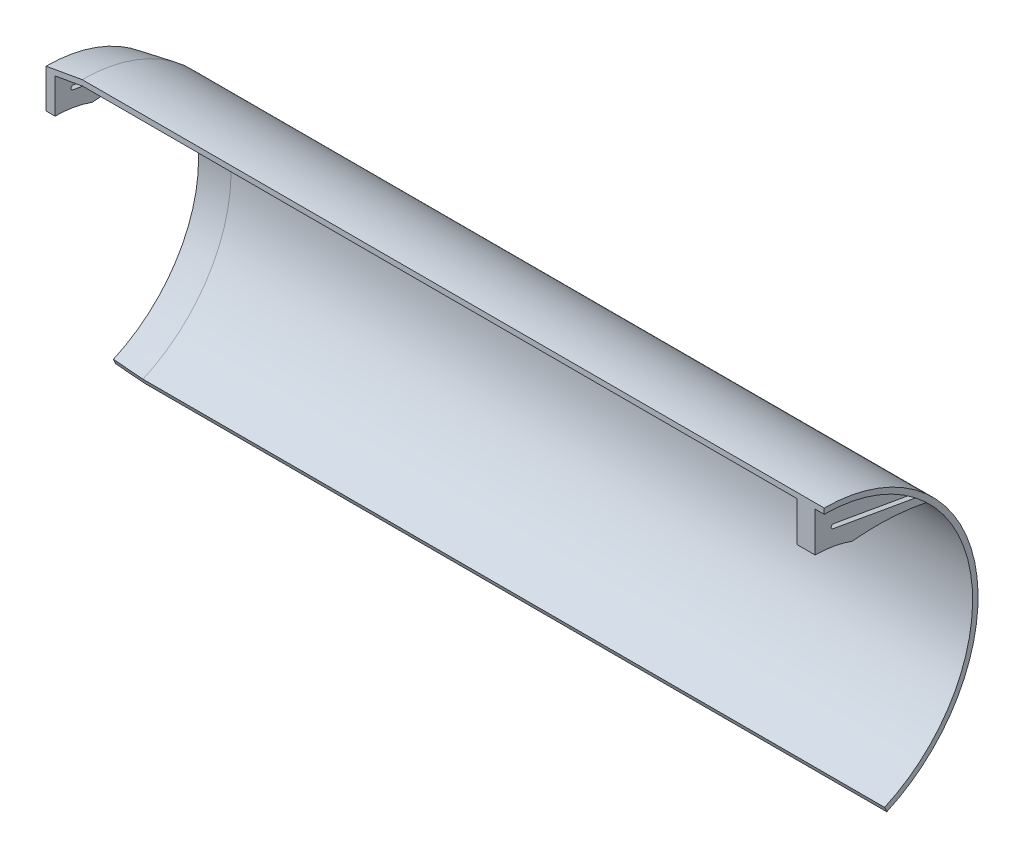
SolidWorks part; units mm, degrees
material "PETG"
ref_plane "Front Plane" through (0, 0, 0) normal (0, 0, 1) x (1, 0, 0)
ref_plane "Top Plane" through (0, 0, 0) normal (0, 1, 0) x (1, 0, 0)
ref_plane "Right Plane" through (0, 0, 0) normal (1, 0, 0) x (0, 0, -1)
curve "Curve1"
  spline degree 3 poles (0, 0, 0) (-0.0123, 3.8916, 0) (-0.0274, 8.685, 0) (0.3616, 14.0857, 0) (0.5761, 16.0905, 0) (0.7825, 17.6048, 0) (0.9862, 18.8543, 0) (1.1887, 19.9315, 0) (1.3904, 20.8857, 0) (1.5917, 21.7465, 0) (1.7927, 22.5337, 0) (1.9935, 23.2611, 0) (2.1942, 23.9386, 0) (2.3947, 24.5739, 0) (2.5952, 25.1728, 0) (2.7956, 25.7401, 0) (2.9959, 26.2796, 0) (3.1962, 26.7943, 0) (3.3965, 27.2868, 0) (3.5967, 27.7594, 0) (3.7969, 28.2139, 0) (3.9971, 28.6519, 0) (4.1973, 29.0748, 0) (4.3974, 29.4838, 0) (4.5976, 29.8799, 0) (4.7977, 30.2641, 0) (4.9978, 30.6373, 0) (5.1979, 31.0001, 0) (5.398, 31.3533, 0) (5.5981, 31.6974, 0) (5.7982, 32.033, 0) (5.9983, 32.3606, 0) (6.1984, 32.6807, 0) (6.3985, 32.9935, 0) (6.5985, 33.2996, 0) (6.7986, 33.5993, 0) (6.9986, 33.8929, 0) (7.1987, 34.1806, 0) (7.3987, 34.4628, 0) (7.5988, 34.7397, 0) (7.7988, 35.0115, 0) (7.9989, 35.2785, 0) (8.1989, 35.5408, 0) (8.399, 35.7988, 0) (8.599, 36.0524, 0) (8.799, 36.3019, 0) (8.9991, 36.5476, 0) (9.1991, 36.7894, 0) (9.3991, 37.0275, 0) (9.5992, 37.2622, 0) (9.7992, 37.4934, 0) (9.9992, 37.7214, 0) (10.1992, 37.9461, 0) (10.3993, 38.1679, 0) (10.5993, 38.3866, 0) (10.7993, 38.6025, 0) (10.9993, 38.8156, 0) (11.1993, 39.026, 0) (11.3994, 39.2338, 0) (11.5994, 39.4391, 0) (11.7994, 39.6419, 0) (11.9994, 39.8422, 0) (12.1994, 40.0403, 0) (12.3995, 40.2361, 0) (12.5995, 40.4297, 0) (12.7995, 40.6212, 0) (12.9995, 40.8106, 0) (13.1995, 40.998, 0) (13.3995, 41.1834, 0) (13.5995, 41.3668, 0) (13.7995, 41.5484, 0) (13.9996, 41.7281, 0) (14.1996, 41.9061, 0) (14.3996, 42.0823, 0) (14.5996, 42.2568, 0) (14.7996, 42.4296, 0) (14.9996, 42.6008, 0) (15.1996, 42.7705, 0) (15.3996, 42.9385, 0) (15.5996, 43.1051, 0) (15.7996, 43.2701, 0) (15.9997, 43.4337, 0) (16.1997, 43.5959, 0) (16.3997, 43.7567, 0) (16.5997, 43.9161, 0) (16.7997, 44.0742, 0) (16.9997, 44.2309, 0) (17.1997, 44.3864, 0) (17.3997, 44.5406, 0) (17.5997, 44.6936, 0) (17.7997, 44.8453, 0) (17.9997, 44.9959, 0) (18.1997, 45.1453, 0) (18.3997, 45.2936, 0) (18.5997, 45.4407, 0) (18.7997, 45.5868, 0) (18.9997, 45.7317, 0) (19.1998, 45.8756, 0) (19.3998, 46.0185, 0) (19.5998, 46.1603, 0) (19.7998, 46.3011, 0) (19.9998, 46.4409, 0) (20.1998, 46.5797, 0) (20.3998, 46.7176, 0) (20.5998, 46.8546, 0) (20.7998, 46.9906, 0) (20.9998, 47.1257, 0) (21.1998, 47.2599, 0) (21.3998, 47.3932, 0) (21.5998, 47.5256, 0) (21.7998, 47.6572, 0) (21.9998, 47.788, 0) (22.1998, 47.9179, 0) (22.3998, 48.047, 0) (22.5998, 48.1753, 0) (22.7998, 48.3028, 0) (22.9998, 48.4295, 0) (23.1998, 48.5555, 0) (23.3998, 48.6807, 0) (23.5998, 48.8051, 0) (23.7998, 48.9288, 0) (23.9998, 49.0518, 0) (24.1998, 49.1741, 0) (24.3998, 49.2957, 0) (24.5998, 49.4165, 0) (24.7999, 49.5367, 0) (24.9999, 49.6562, 0) (25.1999, 49.7751, 0) (25.3999, 49.8933, 0) (25.5999, 50.0108, 0) (25.7999, 50.1277, 0) (25.9999, 50.2439, 0) (26.1999, 50.3596, 0) (26.3999, 50.4746, 0) (26.5999, 50.589, 0) (26.7999, 50.7028, 0) (26.9999, 50.8161, 0) (27.1999, 50.9287, 0) (27.3999, 51.0407, 0) (27.5999, 51.1522, 0) (27.7999, 51.2631, 0) (27.9999, 51.3735, 0) (28.1999, 51.4833, 0) (28.3999, 51.5926, 0) (28.5999, 51.7013, 0) (28.7999, 51.8095, 0) (28.9999, 51.9172, 0) (29.1999, 52.0243, 0) (29.3999, 52.131, 0) (29.5999, 52.2371, 0) (29.7999, 52.3428, 0) (29.9999, 52.4479, 0) (30.1999, 52.5526, 0) (30.3999, 52.6567, 0) (30.5999, 52.7604, 0) (30.7999, 52.8636, 0) (30.9999, 52.9664, 0) (31.1999, 53.0687, 0) (31.3999, 53.1705, 0) (31.5999, 53.2719, 0) (31.7999, 53.3728, 0) (31.9999, 53.4733, 0) (32.1999, 53.5733, 0) (32.3999, 53.6729, 0) (32.5999, 53.7721, 0) (32.7999, 53.8709, 0) (32.9999, 53.9692, 0) (33.1999, 54.0671, 0) (33.3999, 54.1646, 0) (33.5999, 54.2617, 0) (33.7999, 54.3584, 0) (33.9999, 54.4547, 0) (34.1999, 54.5506, 0) (34.3999, 54.6461, 0) (34.5999, 54.7412, 0) (34.7999, 54.836, 0) (34.9999, 54.9303, 0) (35.1999, 55.0243, 0) (35.3999, 55.1179, 0) (35.5999, 55.2111, 0) (35.7999, 55.304, 0) (35.9999, 55.3965, 0) (36.1999, 55.4887, 0) (36.3999, 55.5805, 0) (36.5999, 55.6719, 0) (36.7999, 55.763, 0) (36.9999, 55.8537, 0) (37.1999, 55.9441, 0) (37.3999, 56.0342, 0) (37.5999, 56.1239, 0) (37.7999, 56.2133, 0) (37.9999, 56.3024, 0) (38.1999, 56.3911, 0) (38.3999, 56.4795, 0) (38.5999, 56.5676, 0) (38.7999, 56.6554, 0) (38.9999, 56.7428, 0) (39.1999, 56.83, 0) (39.3999, 56.9168, 0) (39.5999, 57.0033, 0) (39.7999, 57.0896, 0) (39.9999, 57.1755, 0) (40.1999, 57.2611, 0) (40.3999, 57.3464, 0) (40.5999, 57.4314, 0) (40.7999, 57.5161, 0) (40.9999, 57.6006, 0) (41.1999, 57.6847, 0) (41.3999, 57.7686, 0) (41.6, 57.8522, 0) (41.8, 57.9355, 0) (42, 58.0185, 0) (42.2, 58.1012, 0) (42.4, 58.1837, 0) (42.6, 58.2659, 0) (42.8, 58.3479, 0) (43, 58.4295, 0) (43.2, 58.5109, 0) (43.4, 58.592, 0) (43.6, 58.6729, 0) (43.8, 58.7535, 0) (44, 58.8339, 0) (44.2, 58.914, 0) (44.4, 58.9938, 0) (44.6, 59.0734, 0) (44.8, 59.1528, 0) (45, 59.2319, 0) (45.2, 59.3107, 0) (45.4, 59.3893, 0) (45.6, 59.4677, 0) (45.8, 59.5458, 0) (46, 59.6237, 0) (46.2, 59.7014, 0) (46.4, 59.7788, 0) (46.6, 59.856, 0) (46.8, 59.9329, 0) (47, 60.0096, 0) (47.2, 60.0861, 0) (47.4, 60.1624, 0) (47.6, 60.2385, 0) (47.8, 60.3143, 0) (48, 60.3899, 0) (48.2, 60.4652, 0) (48.4, 60.5404, 0) (48.6, 60.6153, 0) (48.8, 60.6901, 0) (49, 60.7646, 0) (49.2, 60.8389, 0) (49.4, 60.913, 0) (49.6, 60.9869, 0) (49.8, 61.0605, 0) (50, 61.134, 0) (50.2, 61.2072, 0) (50.4, 61.2803, 0) (50.6, 61.3531, 0) (50.8, 61.4258, 0) (51, 61.4982, 0) (51.2, 61.5705, 0) (51.4, 61.6426, 0) (51.6, 61.7144, 0) (51.8, 61.7861, 0) (52, 61.8575, 0) (52.2, 61.9288, 0) (52.4, 61.9999, 0) (52.6, 62.0708, 0) (52.8, 62.1415, 0) (53, 62.212, 0) (53.2, 62.2824, 0) (53.4, 62.3525, 0) (53.6, 62.4225, 0) (53.8, 62.4923, 0) (54, 62.5619, 0) (54.2, 62.6313, 0) (54.4, 62.7006, 0) (54.6, 62.7696, 0) (54.8, 62.8385, 0) (55, 62.9072, 0) (55.2, 62.9758, 0) (55.4, 63.0441, 0) (55.6, 63.1123, 0) (55.8, 63.1803, 0) (56, 63.2482, 0) (56.2, 63.3159, 0) (56.4, 63.3834, 0) (56.6, 63.4507, 0) (56.8, 63.5179, 0) (57, 63.5849, 0) (57.2, 63.6518, 0) (57.4, 63.7185, 0) (57.6, 63.785, 0) (57.8, 63.8513, 0) (58, 63.9175, 0) (58.2, 63.9836, 0) (58.4, 64.0495, 0) (58.6, 64.1152, 0) (58.8, 64.1808, 0) (59, 64.2462, 0) (59.2, 64.3114, 0) (59.4, 64.3765, 0) (59.6, 64.4415, 0) (59.8, 64.5063, 0) (60, 64.5709, 0) (60.2, 64.6354, 0) (60.4, 64.6998, 0) (60.6, 64.764, 0) (60.8, 64.828, 0) (61, 64.8919, 0) (61.2, 64.9557, 0) (61.4, 65.0193, 0) (61.6, 65.0827, 0) (61.8, 65.1461, 0) (62, 65.2092, 0) (62.2, 65.2723, 0) (62.4, 65.3352, 0) (62.6, 65.3979, 0) (62.8, 65.4605, 0) (63, 65.523, 0) (63.2, 65.5853, 0) (63.4, 65.6475, 0) (63.6, 65.7096, 0) (63.8, 65.7715, 0) (64, 65.8333, 0) (64.2, 65.895, 0) (64.4, 65.9565, 0) (64.6, 66.0179, 0) (64.8, 66.0791, 0) (65, 66.1402, 0) (65.2, 66.2012, 0) (65.4, 66.2621, 0) (65.6, 66.3228, 0) (65.8, 66.3834, 0) (66, 66.4439, 0) (66.2, 66.5042, 0) (66.4, 66.5644, 0) (66.6, 66.6245, 0) (66.8, 66.6845, 0) (67, 66.7443, 0) (67.2, 66.804, 0) (67.4, 66.8636, 0) (67.6, 66.923, 0) (67.8, 66.9824, 0) (68, 67.0416, 0) (68.2, 67.1007, 0) (68.4, 67.1597, 0) (68.6, 67.2185, 0) (68.8, 67.2772, 0) (69, 67.3359, 0) (69.2, 67.3943, 0) (69.4, 67.4527, 0) (69.6, 67.511, 0) (69.8, 67.5691, 0) (70, 67.6271, 0) (70.2, 67.6851, 0) (70.4, 67.7428, 0) (70.6, 67.8005, 0) (70.8, 67.8581, 0) (71, 67.9155, 0) (71.2, 67.9729, 0) (71.4, 68.0301, 0) (71.6, 68.0872, 0) (71.8, 68.1442, 0) (72, 68.2011, 0) (72.2, 68.2579, 0) (72.4, 68.3145, 0) (72.6, 68.3711, 0) (72.8, 68.4276, 0) (73, 68.4839, 0) (73.2, 68.5401, 0) (73.4, 68.5963, 0) (73.6, 68.6523, 0) (73.8, 68.7082, 0) (74, 68.764, 0) (74.2, 68.8197, 0) (74.4, 68.8753, 0) (74.6, 68.9308, 0) (74.8, 68.9862, 0) (75, 69.0415, 0) (75.2, 69.0966, 0) (75.4, 69.1517, 0) (75.6, 69.2067, 0) (75.8, 69.2616, 0) (76, 69.3164, 0) (76.2, 69.371, 0) (76.4, 69.4256, 0) (76.6, 69.4801, 0) (76.8, 69.5344, 0) (77, 69.5887, 0) (77.2, 69.6429, 0) (77.4, 69.697, 0) (77.6, 69.751, 0) (77.8, 69.8048, 0) (78, 69.8586, 0) (78.2, 69.9123, 0) (78.4, 69.9659, 0) (78.6, 70.0194, 0) (78.8, 70.0728, 0) (79, 70.1261, 0) (79.2, 70.1793, 0) (79.4, 70.2324, 0) (79.6, 70.2855, 0) (79.8, 70.3384, 0) (80, 70.3912, 0) (80.2, 70.444, 0) (80.4, 70.4966, 0) (80.6, 70.5492, 0) (80.8, 70.6017, 0) (81, 70.6541, 0) (81.2, 70.7064, 0) (81.4, 70.7586, 0) (81.6, 70.8107, 0) (81.8, 70.8627, 0) (82, 70.9146, 0) (82.2, 70.9665, 0) (82.4, 71.0182, 0) (82.6, 71.0699, 0) (82.8, 71.1215, 0) (83, 71.173, 0) (83.2, 71.2244, 0) (83.4, 71.2757, 0) (83.6, 71.3269, 0) (83.8, 71.3781, 0) (84, 71.4291, 0) (84.2, 71.4801, 0) (84.4, 71.531, 0) (84.6, 71.5818, 0) (84.8, 71.6325, 0) (85, 71.6832, 0) (85.2, 71.7337, 0) (85.4, 71.7842, 0) (85.6, 71.8346, 0) (85.8, 71.8849, 0) (86, 71.9351, 0) (86.2, 71.9853, 0) (86.4, 72.0354, 0) (86.6, 72.0853, 0) (86.8, 72.1352, 0) (87, 72.1851, 0) (87.2, 72.2348, 0) (87.4, 72.2845, 0) (87.6, 72.3341, 0) (87.8, 72.3836, 0) (88, 72.433, 0) (88.2, 72.4823, 0) (88.4, 72.5316, 0) (88.6, 72.5808, 0) (88.8, 72.6299, 0) (89, 72.6789, 0) (89.2, 72.7279, 0) (89.4, 72.7768, 0) (89.6, 72.8256, 0) (89.8, 72.8743, 0) (90, 72.923, 0) (90.2, 72.9716, 0) (90.4, 73.0201, 0) (90.6, 73.0685, 0) (90.8, 73.1168, 0) (91, 73.1651, 0) (91.2, 73.2133, 0) (91.4, 73.2614, 0) (91.6, 73.3095, 0) (91.8, 73.3575, 0) (92, 73.4054, 0) (92.2, 73.4532, 0) (92.4, 73.501, 0) (92.6, 73.5487, 0) (92.8, 73.5963, 0) (93, 73.6439, 0) (93.2, 73.6913, 0) (93.4, 73.7387, 0) (93.6, 73.7861, 0) (93.8, 73.8333, 0) (94, 73.8805, 0) (94.2, 73.9276, 0) (94.4, 73.9747, 0) (94.6, 74.0217, 0) (94.8, 74.0686, 0) (95, 74.1154, 0) (95.2, 74.1622, 0) (95.4, 74.2089, 0) (95.6, 74.2556, 0) (95.8, 74.3021, 0) (96, 74.3486, 0) (96.2, 74.3951, 0) (96.4, 74.4414, 0) (96.6, 74.4877, 0) (96.8, 74.534, 0) (97, 74.5801, 0) (97.2, 74.6262, 0) (97.4, 74.6723, 0) (97.6, 74.7182, 0) (97.8, 74.7641, 0) (98, 74.81, 0) (98.2, 74.8557, 0) (98.4, 74.9014, 0) (98.6, 74.9471, 0) (98.8, 74.9926, 0) (99, 75.0382, 0) (99.2, 75.0836, 0) (99.4, 75.129, 0) (99.6, 75.1743, 0) (99.8, 75.2196, 0) (100, 75.2647, 0) (100.2, 75.3099, 0) (100.4, 75.3549, 0) (100.6, 75.3999, 0) (100.8, 75.4449, 0) (101, 75.4898, 0) (101.2, 75.5346, 0) (101.4, 75.5793, 0) (101.6, 75.624, 0) (101.8, 75.6686, 0) (102, 75.7132, 0) (102.2, 75.7577, 0) (102.4, 75.8022, 0) (102.6, 75.8465, 0) (102.8, 75.8909, 0) (103, 75.9351, 0) (103.2, 75.9793, 0) (103.4, 76.0235, 0) (103.6, 76.0676, 0) (103.8, 76.1116, 0) (104, 76.1556, 0) (104.2, 76.1995, 0) (104.4, 76.2433, 0) (104.6, 76.2871, 0) (104.8, 76.3308, 0) (105, 76.3745, 0) (105.2, 76.4181, 0) (105.4, 76.4617, 0) (105.6, 76.5052, 0) (105.8, 76.5486, 0) (106, 76.592, 0) (106.2, 76.6353, 0) (106.4, 76.6786, 0) (106.6, 76.7218, 0) (106.8, 76.7649, 0) (107, 76.808, 0) (107.2, 76.8511, 0) (107.4, 76.8941, 0) (107.6, 76.937, 0) (107.8, 76.9799, 0) (108, 77.0227, 0) (108.2, 77.0655, 0) (108.4, 77.1082, 0) (108.6, 77.1508, 0) (108.8, 77.1934, 0) (109, 77.236, 0) (109.2, 77.2784, 0) (109.4, 77.3209, 0) (109.6, 77.3633, 0) (109.8, 77.4056, 0) (110, 77.4479, 0) (110.2, 77.4901, 0) (110.4, 77.5322, 0) (110.6, 77.5743, 0) (110.8, 77.6164, 0) (111, 77.6584, 0) (111.2, 77.7004, 0) (111.4, 77.7423, 0) (111.6, 77.7841, 0) (111.8, 77.8259, 0) (112, 77.8676, 0) (112.2, 77.9093, 0) (112.4, 77.951, 0) (112.6, 77.9925, 0) (112.8, 78.0341, 0) (113, 78.0756, 0) (113.2, 78.117, 0) (113.4, 78.1584, 0) (113.6, 78.1997, 0) (113.8, 78.241, 0) (114, 78.2822, 0) (114.2, 78.3234, 0) (114.4, 78.3645, 0) (114.6, 78.4056, 0) (114.8, 78.4466, 0) (115, 78.4876, 0) (115.2, 78.5285, 0) (115.4, 78.5694, 0) (115.6, 78.6102, 0) (115.8, 78.651, 0) (116, 78.6917, 0) (116.2, 78.7324, 0) (116.4, 78.773, 0) (116.6, 78.8136, 0) (116.8, 78.8541, 0) (117, 78.8946, 0) (117.2, 78.935, 0) (117.4, 78.9754, 0) (117.6, 79.0158, 0) (117.8, 79.0561, 0) (118, 79.0963, 0) (118.2, 79.1365, 0) (118.4, 79.1766, 0) (118.6, 79.2167, 0) (118.8, 79.2568, 0) (119, 79.2968, 0) (119.2, 79.3368, 0) (119.4, 79.3767, 0) (119.6, 79.4165, 0) (119.8, 79.4564, 0) (120, 79.4961, 0) (120.2, 79.5358, 0) (120.4, 79.5755, 0) (120.6, 79.6152, 0) (120.8, 79.6547, 0) (121, 79.6943, 0) (121.2, 79.7338, 0) (121.4, 79.7732, 0) (121.6, 79.8126, 0) (121.8, 79.852, 0) (122, 79.8913, 0) (122.2, 79.9306, 0) (122.4, 79.9698, 0) (122.6, 80.009, 0) (122.8, 80.0481, 0) (123, 80.0872, 0) (123.2, 80.1262, 0) (123.4, 80.1652, 0) (123.6, 80.2042, 0) (123.8, 80.2431, 0) (124, 80.282, 0) (124.2, 80.3208, 0) (124.4, 80.3596, 0) (124.6, 80.3983, 0) (124.8, 80.437, 0) (125, 80.4757, 0) (125.2, 80.5143, 0) (125.4, 80.5528, 0) (125.6, 80.5914, 0) (125.8, 80.6298, 0) (126, 80.6683, 0) (126.2, 80.7067, 0) (126.4, 80.745, 0) (126.6, 80.7833, 0) (126.8, 80.8216, 0) (127, 80.8598, 0) (127.2, 80.898, 0) (127.4, 80.9361, 0) (127.6, 80.9742, 0) (127.8, 81.0123, 0) (128, 81.0503, 0) (128.2, 81.0883, 0) (128.4, 81.1262, 0) (128.6, 81.1641, 0) (128.8, 81.2019, 0) (129, 81.2397, 0) (129.2, 81.2775, 0) (129.4, 81.3152, 0) (129.6, 81.3529, 0) (129.8, 81.3906, 0) (130, 81.4282, 0) (130.2, 81.4657, 0) (130.4, 81.5032, 0) (130.6, 81.5407, 0) (130.8, 81.5782, 0) (131, 81.6156, 0) (131.2, 81.6529, 0) (131.4, 81.6902, 0) (131.6, 81.7275, 0) (131.8, 81.7648, 0) (132, 81.802, 0) (132.2, 81.8391, 0) (132.4, 81.8763, 0) (132.6, 81.9133, 0) (132.8, 81.9504, 0) (133, 81.9874, 0) (133.2, 82.0244, 0) (133.4, 82.0613, 0) (133.6, 82.0982, 0) (133.8, 82.135, 0) (134, 82.1718, 0) (134.2, 82.2086, 0) (134.4, 82.2454, 0) (134.6, 82.282, 0) (134.8, 82.3187, 0) (135, 82.3553, 0) (135.2, 82.3919, 0) (135.4, 82.4285, 0) (135.6, 82.465, 0) (135.8, 82.5014, 0) (136, 82.5379, 0) (136.2, 82.5743, 0) (136.4, 82.6106, 0) (136.6, 82.6469, 0) (136.8, 82.6832, 0) (137, 82.7195, 0) (137.2, 82.7557, 0) (137.4, 82.7919, 0) (137.6, 82.828, 0) (137.8, 82.8641, 0) (138, 82.9001, 0) (138.2, 82.9362, 0) (138.4, 82.9722, 0) (138.6, 83.0081, 0) (138.8, 83.044, 0) (139, 83.0799, 0) (139.2, 83.1158, 0) (139.4, 83.1516, 0) (139.6, 83.1873, 0) (139.8, 83.2231, 0) (140, 83.2588, 0) (140.2, 83.2944, 0) (140.4, 83.3301, 0) (140.6, 83.3657, 0) (140.8, 83.4012, 0) (141, 83.4367, 0) (141.2, 83.4722, 0) (141.4, 83.5077, 0) (141.6, 83.5431, 0) (141.8, 83.5785, 0) (142, 83.6138, 0) (142.2, 83.6491, 0) (142.4, 83.6844, 0) (142.6, 83.7197, 0) (142.8, 83.7549, 0) (143, 83.79, 0) (143.2, 83.8252, 0) (143.4, 83.8603, 0) (143.6, 83.8954, 0) (143.8, 83.9304, 0) (144, 83.9654, 0) (144.2, 84.0004, 0) (144.4, 84.0353, 0) (144.6, 84.0702, 0) (144.8, 84.1051, 0) (145, 84.1399, 0) (145.2, 84.1747, 0) (145.4, 84.2095, 0) (145.6, 84.2442, 0) (145.8, 84.2789, 0) (146, 84.3136, 0) (146.2, 84.3482, 0) (146.4, 84.3828, 0) (146.6, 84.4174, 0) (146.8, 84.4519, 0) (147, 84.4864, 0) (147.2, 84.5209, 0) (147.4, 84.5553, 0) (147.6, 84.5897, 0) (147.8, 84.6241, 0) (148, 84.6584, 0) (148.2, 84.6927, 0) (148.4, 84.727, 0) (148.6, 84.7612, 0) (148.8, 84.7954, 0) (149, 84.8296, 0) (149.2, 84.8638, 0) (149.4, 84.8979, 0) (149.6, 84.9319, 0) (149.8, 84.966, 0) (149.9333, 84.9887, 0) (150, 85, 0) knots 0 0 0 0 0.061462 0.075706 0.085548 0.093322 0.099856 0.105554 0.110643 0.115268 0.119525 0.123482 0.127192 0.130691 0.13401 0.137173 0.140199 0.143104 0.145901 0.148602 0.151215 0.15375 0.156213 0.158609 0.160946 0.163227 0.165456 0.167638 0.169775 0.171871 0.173928 0.17595 0.177937 0.179893 0.181819 0.183716 0.185587 0.187433 0.189255 0.191054 0.192831 0.194589 0.196326 0.198045 0.199747 0.201431 0.2031 0.204753 0.206391 0.208015 0.209626 0.211223 0.212808 0.214381 0.215942 0.217493 0.219032 0.220561 0.22208 0.22359 0.225091 0.226582 0.228065 0.229539 0.231006 0.232464 0.233915 0.235359 0.236795 0.238225 0.239648 0.241065 0.242475 0.243879 0.245277 0.24667 0.248057 0.249438 0.250814 0.252185 0.253551 0.254913 0.256269 0.257621 0.258968 0.260311 0.26165 0.262984 0.264315 0.265641 0.266964 0.268282 0.269598 0.270909 0.272217 0.273522 0.274823 0.276121 0.277416 0.278707 0.279996 0.281281 0.282564 0.283843 0.28512 0.286394 0.287666 0.288935 0.290201 0.291465 0.292726 0.293985 0.295241 0.296495 0.297747 0.298996 0.300243 0.301489 0.302732 0.303972 0.305211 0.306448 0.307683 0.308916 0.310147 0.311376 0.312604 0.313829 0.315053 0.316275 0.317495 0.318714 0.319931 0.321147 0.32236 0.323573 0.324783 0.325993 0.3272 0.328406 0.329611 0.330815 0.332017 0.333217 0.334416 0.335614 0.336811 0.338006 0.3392 0.340393 0.341584 0.342775 0.343964 0.345152 0.346339 0.347524 0.348709 0.349892 0.351074 0.352256 0.353436 0.354615 0.355793 0.35697 0.358146 0.359321 0.360495 0.361668 0.36284 0.364011 0.365182 0.366351 0.36752 0.368687 0.369854 0.37102 0.372185 0.373349 0.374512 0.375674 0.376836 0.377997 0.379157 0.380316 0.381475 0.382632 0.383789 0.384946 0.386101 0.387256 0.38841 0.389563 0.390716 0.391868 0.393019 0.39417 0.39532 0.396469 0.397618 0.398766 0.399913 0.40106 0.402206 0.403351 0.404496 0.40564 0.406784 0.407927 0.409069 0.410211 0.411353 0.412493 0.413633 0.414773 0.415912 0.417051 0.418189 0.419326 0.420463 0.4216 0.422736 0.423871 0.425006 0.426141 0.427275 0.428408 0.429541 0.430674 0.431806 0.432937 0.434068 0.435199 0.436329 0.437459 0.438588 0.439717 0.440846 0.441974 0.443101 0.444229 0.445355 0.446482 0.447608 0.448733 0.449858 0.450983 0.452107 0.453231 0.454355 0.455478 0.456601 0.457723 0.458845 0.459967 0.461088 0.462209 0.46333 0.46445 0.46557 0.46669 0.467809 0.468928 0.470046 0.471164 0.472282 0.4734 0.474517 0.475634 0.47675 0.477866 0.478982 0.480098 0.481213 0.482328 0.483443 0.484557 0.485671 0.486785 0.487898 0.489011 0.490124 0.491237 0.492349 0.493461 0.494573 0.495684 0.496796 0.497906 0.499017 0.500127 0.501237 0.502347 0.503457 0.504566 0.505675 0.506784 0.507892 0.509001 0.510109 0.511216 0.512324 0.513431 0.514538 0.515645 0.516752 0.517858 0.518964 0.52007 0.521175 0.522281 0.523386 0.524491 0.525595 0.5267 0.527804 0.528908 0.530012 0.531116 0.532219 0.533322 0.534425 0.535528 0.53663 0.537733 0.538835 0.539937 0.541038 0.54214 0.543241 0.544342 0.545443 0.546544 0.547644 0.548745 0.549845 0.550945 0.552044 0.553144 0.554243 0.555342 0.556441 0.55754 0.558639 0.559737 0.560836 0.561934 0.563032 0.564129 0.565227 0.566324 0.567421 0.568518 0.569615 0.570712 0.571809 0.572905 0.574001 0.575097 0.576193 0.577289 0.578384 0.57948 0.580575 0.58167 0.582765 0.58386 0.584954 0.586049 0.587143 0.588237 0.589331 0.590425 0.591519 0.592612 0.593706 0.594799 0.595892 0.596985 0.598078 0.59917 0.600263 0.601355 0.602448 0.60354 0.604632 0.605724 0.606815 0.607907 0.608998 0.61009 0.611181 0.612272 0.613363 0.614453 0.615544 0.616635 0.617725 0.618815 0.619905 0.620995 0.622085 0.623175 0.624265 0.625354 0.626443 0.627533 0.628622 0.629711 0.6308 0.631888 0.632977 0.634066 0.635154 0.636242 0.637331 0.638419 0.639507 0.640594 0.641682 0.64277 0.643857 0.644945 0.646032 0.647119 0.648206 0.649293 0.65038 0.651467 0.652553 0.65364 0.654726 0.655813 0.656899 0.657985 0.659071 0.660157 0.661243 0.662328 0.663414 0.664499 0.665585 0.66667 0.667755 0.66884 0.669925 0.67101 0.672095 0.67318 0.674264 0.675349 0.676433 0.677518 0.678602 0.679686 0.68077 0.681854 0.682938 0.684022 0.685105 0.686189 0.687272 0.688356 0.689439 0.690522 0.691605 0.692688 0.693771 0.694854 0.695937 0.69702 0.698102 0.699185 0.700267 0.70135 0.702432 0.703514 0.704596 0.705678 0.70676 0.707842 0.708924 0.710006 0.711087 0.712169 0.71325 0.714332 0.715413 0.716494 0.717575 0.718656 0.719737 0.720818 0.721899 0.72298 0.724061 0.725141 0.726222 0.727302 0.728382 0.729463 0.730543 0.731623 0.732703 0.733783 0.734863 0.735943 0.737023 0.738103 0.739182 0.740262 0.741341 0.742421 0.7435 0.744579 0.745659 0.746738 0.747817 0.748896 0.749975 0.751054 0.752133 0.753211 0.75429 0.755369 0.756447 0.757526 0.758604 0.759682 0.760761 0.761839 0.762917 0.763995 0.765073 0.766151 0.767229 0.768307 0.769385 0.770462 0.77154 0.772618 0.773695 0.774773 0.77585 0.776927 0.778005 0.779082 0.780159 0.781236 0.782313 0.78339 0.784467 0.785544 0.786621 0.787698 0.788774 0.789851 0.790928 0.792004 0.793081 0.794157 0.795233 0.79631 0.797386 0.798462 0.799538 0.800614 0.80169 0.802766 0.803842 0.804918 0.805994 0.80707 0.808145 0.809221 0.810296 0.811372 0.812447 0.813523 0.814598 0.815674 0.816749 0.817824 0.818899 0.819974 0.821049 0.822124 0.823199 0.824274 0.825349 0.826424 0.827499 0.828573 0.829648 0.830723 0.831797 0.832872 0.833946 0.835021 0.836095 0.837169 0.838244 0.839318 0.840392 0.841466 0.84254 0.843614 0.844688 0.845762 0.846836 0.84791 0.848984 0.850058 0.851131 0.852205 0.853279 0.854352 0.855426 0.856499 0.857573 0.858646 0.859719 0.860793 0.861866 0.862939 0.864012 0.865085 0.866159 0.867232 0.868305 0.869378 0.87045 0.871523 0.872596 0.873669 0.874742 0.875814 0.876887 0.87796 0.879032 0.880105 0.881177 0.88225 0.883322 0.884395 0.885467 0.886539 0.887611 0.888684 0.889756 0.890828 0.8919 0.892972 0.894044 0.895116 0.896188 0.89726 0.898332 0.899404 0.900475 0.901547 0.902619 0.90369 0.904762 0.905834 0.906905 0.907977 0.909048 0.91012 0.911191 0.912262 0.913334 0.914405 0.915476 0.916548 0.917619 0.91869 0.919761 0.920832 0.921903 0.922974 0.924045 0.925116 0.926187 0.927258 0.928329 0.929399 0.93047 0.931541 0.932612 0.933682 0.934753 0.935823 0.936894 0.937965 0.939035 0.940105 0.941176 0.942246 0.943317 0.944387 0.945457 0.946527 0.947598 0.948668 0.949738 0.950808 0.951878 0.952948 0.954018 0.955088 0.956158 0.957228 0.958298 0.959368 0.960438 0.961508 0.962577 0.963647 0.964717 0.965786 0.966856 0.967926 0.968995 0.970065 0.971134 0.972204 0.973273 0.974343 0.975412 0.976481 0.977551 0.97862 0.979689 0.980759 0.981828 0.982897 0.983966 0.985035 0.986104 0.987173 0.988242 0.989311 0.99038 0.991449 0.992518 0.993587 0.994656 0.995725 0.996794 0.997863 0.998931 1 1 1 1
sketch "Sketch1" plane through (0, 0, 0) normal (0, 0, 1) x (1, 0, 0)
  line L0 (150, 85) -> (560, 85)
  line L1 (150.2533, 82) -> (560, 82)
  line L2 (560, 85) -> (560, 82)
  line L3 (0, 0) -> (3, 0)
  line L4 (3, 0.0095) -> (3, 0)
  line L5 (3, 0) -> (560, 0) construction
  line L6 (560, 0) -> (560, 82) construction
  line L8 (140, -75) -> (540, -75) construction
  line L9 (130, 78.3755) -> (135, 78.3755)
  line L10 (140, -75) -> (140, 75) construction
  line L11 (140, 75) -> (540, 75) construction
  line L12 (135, 79.3054) -> (135, 60)
  line L13 (135, 60) -> (130, 60)
  line L14 (130, 60) -> (130, 81.4281)
  line L15 (555, 60) -> (555, 82)
  line L16 (545, 82) -> (545, 60)
  line L17 (545, 60) -> (555, 60)
  line L18 (540, -75) -> (540, 75) construction
  line L19 (140, -75) -> (540, 75) construction
  line L20 (140, 75) -> (540, -75) construction
  spline S0 degree 3 poles (-1988.6566, -159.7184) (98.3599, -158.1291) (-5.7084, -70.1856) (0.3616, 14.0857) (0.5761, 16.0905) (0.7825, 17.6048) (0.9862, 18.8543) (1.1887, 19.9315) (1.3904, 20.8857) (1.5917, 21.7465) (1.7927, 22.5337) (1.9935, 23.2611) (2.2538, 24.14) (2.5806, 25.1462) (2.9836, 26.2595) (3.3859, 27.2713) (3.7877, 28.2016) (4.1891, 29.0648) (4.5903, 29.8717) (5.0533, 30.7478) (5.5832, 31.6835) (6.1854, 32.6697) (6.7872, 33.5906) (7.4515, 34.5461) (8.1828, 35.531) (8.9851, 36.54) (9.8503, 37.5625) (10.7826, 38.5957) (11.785, 39.6369) (12.851, 40.6804) (13.984, 41.7246) (15.1862, 42.7682) (16.388, 43.7553) (17.6544, 44.7435) (18.9876, 45.7315) (20.3892, 46.7179) (21.7905, 47.6579) (23.2571, 48.5984) (24.7904, 49.5382) (26.3916, 50.4762) (28.0583, 51.4122) (29.7917, 52.3451) (31.5927, 53.2742) (33.4594, 54.1996) (35.3929, 55.1207) (37.4597, 56.0672) (39.5933, 57.0066) (41.8602, 57.9666) (44.1937, 58.9175) (46.6606, 59.8853) (49.2604, 60.8677) (51.994, 61.8617) (54.861, 62.8656) (57.7946, 63.8556) (60.8615, 64.8536) (64.0615, 65.8584) (67.4615, 66.8882) (70.9951, 67.9202) (74.6621, 68.9539) (78.4621, 69.9886) (82.4622, 71.0404) (86.6623, 72.1071) (91.0624, 73.1864) (95.6625, 74.2764) (100.4626, 75.3753) (105.4628, 76.4816) (110.6629, 77.5938) (116.063, 78.7107) (121.6632, 79.8312) (127.5299, 80.9671) (133.6633, 82.1162) (140.0634, 83.2764) (145.1985, 84.1774) (148.3332, 84.7158) (149.3333, 84.8865) (149.6, 84.9319) (194.4783, 92.5723) (239.7917, 97.2513) (-50.3187, 2073.1568) knots -1.249314 -1.249314 -1.249314 -1.249314 0.061462 0.075706 0.085548 0.093322 0.099856 0.105554 0.110643 0.115268 0.119525 0.123482 0.127192 0.13401 0.140199 0.145901 0.151215 0.156213 0.160946 0.165456 0.171871 0.177937 0.183716 0.189255 0.196326 0.2031 0.209626 0.217493 0.225091 0.232464 0.241065 0.249438 0.257621 0.265641 0.274823 0.283843 0.292726 0.301489 0.311376 0.321147 0.330815 0.341584 0.352256 0.36284 0.374512 0.386101 0.398766 0.411353 0.425006 0.438588 0.453231 0.468928 0.484557 0.501237 0.517858 0.535528 0.554243 0.574001 0.593706 0.614453 0.636242 0.659071 0.682938 0.707842 0.733783 0.760761 0.788774 0.817824 0.84791 0.879032 0.912262 0.946527 0.981828 0.994656 0.996794 0.997863 0.998931 1.716252 1.716252 1.716252 1.716252 only from (0, 0) to (150, 85) construction
  spline S1 degree 3 poles (0, 0) (-0.0123, 3.8916) (-0.0274, 8.685) (0.3616, 14.0857) (0.5761, 16.0905) (0.7825, 17.6048) (0.9862, 18.8543) (1.1887, 19.9315) (1.3904, 20.8857) (1.5917, 21.7465) (1.7927, 22.5337) (1.9935, 23.2611) (2.2538, 24.14) (2.5806, 25.1462) (2.9836, 26.2595) (3.3859, 27.2713) (3.7877, 28.2016) (4.1891, 29.0648) (4.5903, 29.8717) (5.0533, 30.7478) (5.5832, 31.6835) (6.1854, 32.6697) (6.7872, 33.5906) (7.4515, 34.5461) (8.1828, 35.531) (8.9851, 36.54) (9.8503, 37.5625) (10.7826, 38.5957) (11.785, 39.6369) (12.851, 40.6804) (13.984, 41.7246) (15.1862, 42.7682) (16.388, 43.7553) (17.6544, 44.7435) (18.9876, 45.7315) (20.3892, 46.7179) (21.7905, 47.6579) (23.2571, 48.5984) (24.7904, 49.5382) (26.3916, 50.4762) (28.0583, 51.4122) (29.7917, 52.3451) (31.5927, 53.2742) (33.4594, 54.1996) (35.3929, 55.1207) (37.4597, 56.0672) (39.5933, 57.0066) (41.8602, 57.9666) (44.1937, 58.9175) (46.6606, 59.8853) (49.2604, 60.8677) (51.994, 61.8617) (54.861, 62.8656) (57.7946, 63.8556) (60.8615, 64.8536) (64.0615, 65.8584) (67.4615, 66.8882) (70.9951, 67.9202) (74.6621, 68.9539) (78.4621, 69.9886) (82.4622, 71.0404) (86.6623, 72.1071) (91.0624, 73.1864) (95.6625, 74.2764) (100.4626, 75.3753) (105.4628, 76.4816) (110.6629, 77.5938) (116.063, 78.7107) (121.6632, 79.8312) (127.5299, 80.9671) (133.6633, 82.1162) (140.0634, 83.2764) (145.1985, 84.1774) (148.3332, 84.7158) (149.4, 84.8979) (149.7333, 84.9547) (149.9333, 84.9887) (150, 85) knots 0 0 0 0 0.061462 0.075706 0.085548 0.093322 0.099856 0.105554 0.110643 0.115268 0.119525 0.123482 0.127192 0.13401 0.140199 0.145901 0.151215 0.156213 0.160946 0.165456 0.171871 0.177937 0.183716 0.189255 0.196326 0.2031 0.209626 0.217493 0.225091 0.232464 0.241065 0.249438 0.257621 0.265641 0.274823 0.283843 0.292726 0.301489 0.311376 0.321147 0.330815 0.341584 0.352256 0.36284 0.374512 0.386101 0.398766 0.411353 0.425006 0.438588 0.453231 0.468928 0.484557 0.501237 0.517858 0.535528 0.554243 0.574001 0.593706 0.614453 0.636242 0.659071 0.682938 0.707842 0.733783 0.760761 0.788774 0.817824 0.84791 0.879032 0.912262 0.946527 0.981828 0.994656 0.996794 0.998931 1 1 1 1
  spline S4 degree 1 poles (3, 0.0095) (150.2533, 82) knots 0 0 1 1 construction
  spline S5 degree 3 poles (3, 0.0095) (2.9938, 1.9694) (2.982, 5.9112) (3.1447, 11.6915) (3.6709, 17.3262) (4.8192, 22.7297) (6.752, 27.816) (10.434, 34.0689) (16.886, 40.7698) (26.3115, 47.2193) (36.5885, 52.5329) (47.3393, 57.0416) (62.0527, 62.2707) (80.8898, 67.7174) (103.8331, 73.1782) (119.8433, 76.4414) (128.9979, 78.1869) (130.8328, 78.5327) (132.4993, 78.8436) (134.1662, 79.1526) (140.0771, 80.2373) (145.5819, 81.205) (150.2533, 82) knots 0 0 0 0 0.031208 0.062417 0.093625 0.124833 0.156041 0.18725 0.249666 0.312083 0.374499 0.436916 0.499332 0.624165 0.748998 0.873831 0.883277 0.89671 0.903427 0.910144 0.923577 0.998664 0.998664 0.998664 0.998664
  point P8 (340, 0)
  dimension "D2" = 410
  dimension "D1" = 5
  dimension "D7" = 10
  dimension "D9" = 10
  dimension "D4" = 20
  dimension "D5" = 5
  dimension "D6" = 400
  dimension "D10" = 150
  dimension "D8" = 120
  dimension "D3" = 3
revolve "Revolve5" add sketch "Sketch1" angle 156 about L5 region at (344.8477, 83.4159, 0) region at (133.3296, 78.6861, 0) region at (132.5, 69.1877, 0) region at (550, 71, 0) reverse direction yes
ref_axis "Axis1" through (150, -77.6514, -34.5726) along (1, 0, 0)
ref_plane "Plane1" through (135, 0, 0) normal (1, 0, 0) x (0, 0, -1)
sketch "Sketch4" plane through (135, 0, 0) normal (-1, 0, 0) x (0, 0, 1)
  line L0 (0, 0) -> (-28.1672, 77.3887) construction
  line L1 (0, -89.4583) -> (0, 89.4583) construction
  line L2 (0, 60) -> (0, 82.3553)
  line L6 (0, 0) -> (-10.4189, 59.0885) construction
  line L7 (-57.113, 59.3338) -> (-9.8003, 67.6764)
  line L8 (-53.9452, 62.2279) -> (-10.1997, 69.9414)
  arc A1 (0, 82.3553) -> (-33.4969, -75.2353) centre (0, 0) ccw
  arc A2 (0, 82.3553) -> (-53.9452, 62.2279) centre (0, 0) ccw
  arc A5 (0, 60) -> (-24.4042, -54.8127) centre (0, 0) ccw construction
  arc A8 (0, 60) -> (-20.5212, 56.3816) centre (0, 0) ccw
  arc A9 (-9.8003, 67.6764) -> (-10.1997, 69.9414) centre (-10, 68.8089) ccw
  arc A10 (-20.5212, 56.3816) -> (-61.9052, 54.3153) centre (-34.5726, -77.6514) ccw
  arc A11 (-57.113, 59.3338) -> (-61.9052, 54.3153) centre (0, 0) ccw
  point P5 (-10.4189, 59.0885)
  point P14 (-20.5212, 56.3816)
  dimension "D2" = 8.35
  dimension "D3" = 2.3
  dimension "D4" = 10
  dimension "D1" = 20
extrude "Cut-Extrude2" cut sketch "Sketch4" along normal blind 170 flip side to cut
sketch "Sketch5" plane through (555, 0, 0) normal (1, 0, 0) x (0, 0, -1)
  line L0 (9.8003, 67.6764) -> (51.4774, 60.3275) construction
  line L1 (47.7475, 63.3207) -> (10.1997, 69.9414) construction
  line L6 (0, 85) -> (0, 82)
  line L8 (33.3524, -74.9107) -> (34.5726, -77.6514)
  line L9 (0, 85) -> (0, 60)
  line L10 (33.3524, -74.9107) -> (34.5726, -77.6514)
  line L11 (9.8003, 67.6764) -> (56.4827, 59.445)
  line L12 (53.2601, 62.3487) -> (10.1997, 69.9414)
  arc A0 (20.5212, 56.3816) -> (0, 60) centre (0, 0) ccw construction
  arc A1 (56.887, 55.2559) -> (20.5212, 56.3816) centre (34.5726, -77.6514) ccw construction
  arc A2 (33.3524, -74.9107) -> (0, 82) centre (0, 0) ccw
  arc A3 (34.5726, -77.6514) -> (0, 85) centre (0, 0) ccw
  arc A4 (33.3524, -74.9107) -> (61.3267, 54.4338) centre (0, 0) ccw
  arc A9 (34.5726, -77.6514) -> (0, 85) centre (0, 0) ccw
  arc A23 (10.1997, 69.9414) -> (9.8003, 67.6764) centre (10, 68.8089) ccw construction
  arc A24 (20.5212, 56.3816) -> (0, 60) centre (0, 0) ccw
  arc A27 (61.3267, 54.4338) -> (20.5212, 56.3816) centre (34.5726, -77.6514) ccw
  arc A34 (10.1997, 69.9414) -> (9.8003, 67.6764) centre (10, 68.8089) ccw
  arc A35 (56.4827, 59.445) -> (53.2601, 62.3487) centre (0, 0) ccw
  dimension "D1" = 0
extrude "Cut-Extrude3" cut sketch "Sketch5" against normal blind 10 and the other way through all flip side to cut
equation "\"CanSat_Len\"= 400mm"
equation "\"CanSat_Dia\"= 150mm"
equation "\"BodyTube_ID\"= 114mm"
equation "\"BodyTube_OD\"= 120mm"
equation "\"PayLoadBay_ID\"= 164mm"
equation "\"PayLoadBay_OD\"= 170mm"
equation "\"ParachuteBay_Pitch\"= 400mm"
equation "\"ElectronicsTray_PitchDist\"= 50mm"
equation "\"ElectronicsTray_Height\"= 140mm"
equation "\"MotorDia\"= 98mm"
equation "\"MotorLen\"=289mm"
equation "\"NosePlateDia\"= 156.6mm"
equation "\"D10@Sketch1\"=\"CanSat_Dia\""
equation "\"D6@Sketch1\"=\"CanSat_Len\""
